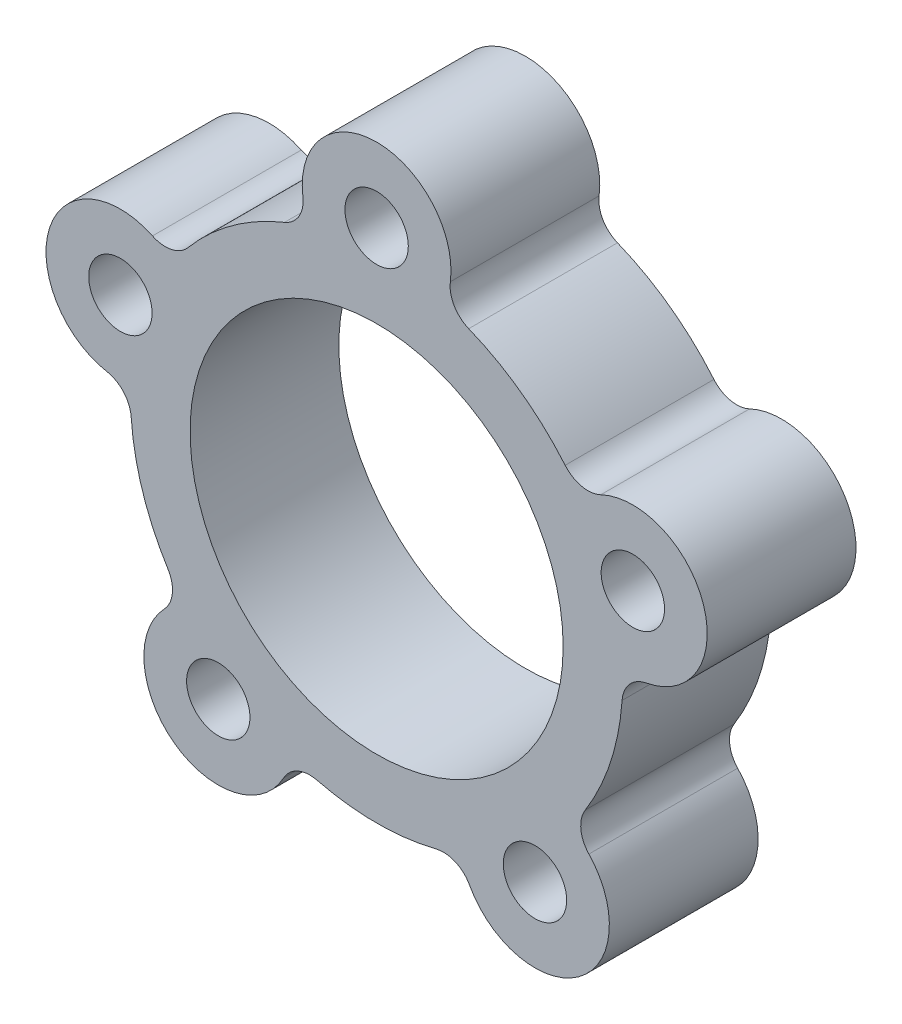
SolidWorks part; units mm, degrees
material "6061-T6 (SS)"
ref_plane "Front Plane" through (0, 0, 0) normal (0, 0, 1) x (1, 0, 0)
ref_plane "Top Plane" through (0, 0, 0) normal (0, 1, 0) x (1, 0, 0)
ref_plane "Right Plane" through (0, 0, 0) normal (1, 0, 0) x (0, 0, -1)
sketch "Sketch1" plane through (0, 0, 7.874) normal (0, 0, 1) x (1, 0, 0)
  circle A1 centre (0, 0) radius 7.9629
  circle A2 centre (0, 0) radius 7.9629
  arc A10 (8.0479, 6.7485) -> (3.9313, 9.7394) centre (0, 0) ccw
  arc A11 (3.1476, 11.0836) -> (-3.1476, 11.0836) centre (0, 11.5) ccw
  arc A12 (-3.9313, 9.7394) -> (-8.0479, 6.7485) centre (0, 0) ccw
  arc A13 (-9.5685, 6.4186) -> (-11.5138, 0.4315) centre (-10.9371, 3.5537) ccw
  arc A14 (-10.4776, -0.7292) -> (-8.9051, -5.5686) centre (0, 0) ccw
  arc A15 (-9.0612, -7.1167) -> (-3.9684, -10.817) centre (-6.7595, -9.3037) ccw
  arc A16 (-2.5442, -10.1901) -> (2.5442, -10.1901) centre (0, 0) ccw
  arc A17 (3.9684, -10.817) -> (9.0612, -7.1167) centre (6.7595, -9.3037) ccw
  arc A18 (8.9051, -5.5686) -> (10.4776, -0.7292) centre (0, 0) ccw
  arc A19 (11.5138, 0.4315) -> (9.5685, 6.4186) centre (10.9371, 3.5537) ccw
  arc A20 (8.0479, 6.7485) -> (3.9313, 9.7394) centre (0, 0) ccw
  arc A21 (3.1476, 11.0836) -> (-3.1476, 11.0836) centre (0, 11.5) ccw
  arc A22 (-3.9313, 9.7394) -> (-8.0479, 6.7485) centre (0, 0) ccw
  arc A23 (-9.5685, 6.4186) -> (-11.5138, 0.4315) centre (-10.9371, 3.5537) ccw
  arc A24 (-10.4776, -0.7292) -> (-8.9051, -5.5686) centre (0, 0) ccw
  arc A25 (-9.0612, -7.1167) -> (-3.9684, -10.817) centre (-6.7595, -9.3037) ccw
  arc A26 (-2.5442, -10.1901) -> (2.5442, -10.1901) centre (0, 0) ccw
  arc A27 (3.9684, -10.817) -> (9.0612, -7.1167) centre (6.7595, -9.3037) ccw
  arc A28 (8.9051, -5.5686) -> (10.4776, -0.7292) centre (0, 0) ccw
  arc A29 (11.5138, 0.4315) -> (9.5685, 6.4186) centre (10.9371, 3.5537) ccw
  arc A72 (8.0479, 6.7485) -> (9.5685, 6.4186) centre (9.0211, 7.5645) ccw
  arc A73 (8.0479, 6.7485) -> (9.5685, 6.4186) centre (9.0211, 7.5645) ccw
  arc A74 (3.1476, 11.0836) -> (3.9313, 9.7394) centre (4.4066, 10.9171) ccw
  arc A75 (3.1476, 11.0836) -> (3.9313, 9.7394) centre (4.4066, 10.9171) ccw
  arc A76 (-3.9313, 9.7394) -> (-3.1476, 11.0836) centre (-4.4066, 10.9171) ccw
  arc A77 (-3.9313, 9.7394) -> (-3.1476, 11.0836) centre (-4.4066, 10.9171) ccw
  arc A78 (-9.5685, 6.4186) -> (-8.0479, 6.7485) centre (-9.0211, 7.5645) ccw
  arc A79 (-9.5685, 6.4186) -> (-8.0479, 6.7485) centre (-9.0211, 7.5645) ccw
  arc A80 (-10.4776, -0.7292) -> (-11.5138, 0.4315) centre (-11.7445, -0.8174) ccw
  arc A81 (-10.4776, -0.7292) -> (-11.5138, 0.4315) centre (-11.7445, -0.8174) ccw
  arc A82 (-9.0612, -7.1167) -> (-8.9051, -5.5686) centre (-9.9819, -6.242) ccw
  arc A83 (-9.0612, -7.1167) -> (-8.9051, -5.5686) centre (-9.9819, -6.242) ccw
  arc A84 (-2.5442, -10.1901) -> (-3.9684, -10.817) centre (-2.8519, -11.4223) ccw
  arc A85 (-2.5442, -10.1901) -> (-3.9684, -10.817) centre (-2.8519, -11.4223) ccw
  arc A86 (3.9684, -10.817) -> (2.5442, -10.1901) centre (2.8519, -11.4223) ccw
  arc A87 (3.9684, -10.817) -> (2.5442, -10.1901) centre (2.8519, -11.4223) ccw
  arc A88 (8.9051, -5.5686) -> (9.0612, -7.1167) centre (9.9819, -6.242) ccw
  arc A89 (8.9051, -5.5686) -> (9.0612, -7.1167) centre (9.9819, -6.242) ccw
  arc A90 (11.5138, 0.4315) -> (10.4776, -0.7292) centre (11.7445, -0.8174) ccw
  arc A91 (11.5138, 0.4315) -> (10.4776, -0.7292) centre (11.7445, -0.8174) ccw
  dimension "D1" = 0
  dimension "D2" = 0
extrude "Boss-Extrude1" add sketch "Sketch1" along normal blind 6.35
hole_wizard "#6-32 Tapped Hole1" positions "Sketch4" profile "Sketch3" tap size "#6-32" standard "ANSI Inch" end condition through all
sketch "Sketch4" plane through (0, 0, 14.224) normal (0, 0, 1) x (1, 0, 0)
  point P0 (-10.9371, 3.5537)
  point P3 (0, 11.5)
  point P6 (10.9371, 3.5537)
  point P9 (6.7595, -9.3037)
  point P12 (-6.7595, -9.3037)
sketch "Sketch3" plane through (-10.9371, 3.5537, 14.224) normal (1, 0, 0) x (0, -1, 0)
  line L0 (0, 0) -> (0, 6.35)
  line L1 (0, 6.35) -> (1.3525, 6.35)
  line L2 (1.3525, 6.35) -> (1.3525, 0)
  line L5 (1.3525, 0) -> (0, 0)
  line L11 (0, -6.35) -> (0, 107.95) construction
  dimension "Thru Tap Drill Dia." = 2.7051
  dimension "Thru Tap Drill Depth" = 6.35
cosmetic thread "Hole Thread1" parameters "D2"=3.5052
cosmetic thread "Hole Thread2" parameters "D2"=3.5052
cosmetic thread "Hole Thread3" parameters "D2"=3.5052
cosmetic thread "Hole Thread4" parameters "D2"=3.5052
cosmetic thread "Hole Thread5" parameters "D2"=3.5052
